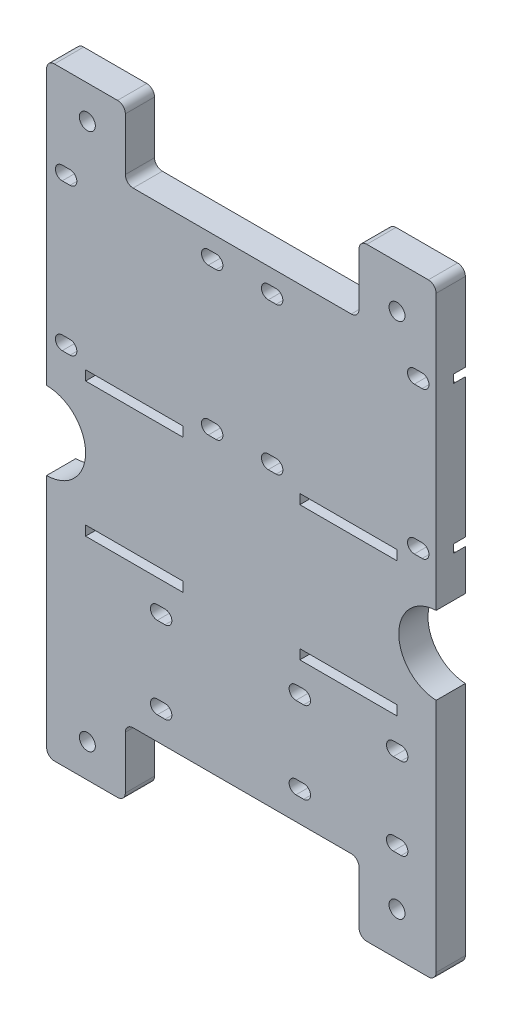
SolidWorks part; units mm, degrees
material "ABS"
ref_plane "Front Plane" through (0, 0, 0) normal (0, 0, 1) x (1, 0, 0)
ref_plane "Top Plane" through (0, 0, 0) normal (0, 1, 0) x (1, 0, 0)
ref_plane "Right Plane" through (0, 0, 0) normal (1, 0, 0) x (0, 0, -1)
sketch "Sketch1" plane through (0, 0, 0) normal (0, 0, 1) x (1, 0, 0)
  line L1 (0, 0) -> (100, 0)
  line L2 (0, 0) -> (0, 155)
  line L3 (0, 155) -> (100, 155)
  line L4 (100, 0) -> (100, 155)
  dimension "D1" = 100
  dimension "D2" = 155
extrude "Boss-Extrude1" add sketch "Sketch1" along normal blind 7.5
sketch "Sketch2" plane through (0, 0, 7.5) normal (0, 0, 1) x (1, 0, 0)
  line L0 (0, 77.5) -> (100, 77.5) construction
  line L1 (0, 155) -> (0, 0) construction
  line L2 (100, 0) -> (100, 155) construction
  line L3 (100, 155) -> (0, 155) construction
  line L4 (10.45, 146.45) -> (20.2, 146.45) construction
  line L5 (20.2, 137.5) -> (80.2, 137.5)
  line L6 (20.2, 137.5) -> (20.2, 155)
  line L7 (20.2, 155) -> (80.2, 155)
  line L8 (80.2, 137.5) -> (80.2, 155)
  line L9 (89.95, 143.95) -> (80.2, 143.95) construction
  line L10 (20.2, 0) -> (80.2, 0)
  line L11 (80.2, 17.5) -> (80.2, 0)
  line L12 (20.2, 17.5) -> (80.2, 17.5)
  line L13 (20.2, 17.5) -> (20.2, 0)
  circle A0 centre (10.45, 146.45) radius 2.05
  circle A1 centre (89.95, 143.95) radius 2.05
  circle A2 centre (89.95, 11.05) radius 2.05
  circle A3 centre (10.45, 8.55) radius 2.05
  dimension "D5" = 4.1
  dimension "D1" = 8.55
  dimension "D2" = 89.55
  dimension "D3" = 10.05
  dimension "D4" = 11.05
  dimension "D6" = 17.5
  dimension "D7" = 60
extrude "Hole cutouts" cut sketch "Sketch2" against normal through all
sketch "Sketch3" plane through (0, 0, 7.5) normal (0, 0, 1) x (1, 0, 0)
  line L0 (0, 72.5) -> (100, 72.5) construction
  line L1 (0, 155) -> (0, 0) construction
  line L2 (100, 0) -> (100, 155) construction
  line L3 (90, 56.5) -> (90, 54)
  line L4 (0, 56.5) -> (100, 56.5)
  line L5 (0, 56.5) -> (0, 88.5)
  line L6 (0, 88.5) -> (100, 88.5)
  line L7 (100, 56.5) -> (100, 88.5)
  line L8 (0, 56.5) -> (100, 88.5) construction
  line L9 (0, 88.5) -> (100, 56.5) construction
  line L10 (10, 88.5) -> (35, 88.5)
  line L11 (10, 88.5) -> (10, 91)
  line L12 (10, 91) -> (35, 91)
  line L13 (35, 88.5) -> (35, 91)
  line L14 (65, 88.5) -> (90, 88.5)
  line L15 (65, 88.5) -> (65, 91)
  line L16 (65, 91) -> (90, 91)
  line L17 (90, 88.5) -> (90, 91)
  line L18 (65, 54) -> (90, 54)
  line L19 (65, 56.5) -> (65, 54)
  line L20 (35, 56.5) -> (35, 54)
  line L21 (10, 56.5) -> (10, 54)
  line L22 (10, 54) -> (35, 54)
  line L23 (10, 56.5) -> (35, 56.5)
  line L24 (65, 56.5) -> (90, 56.5)
  point P6 (50, 72.5)
  point P27 (0, 77.5)
  dimension "D1" = 32
  dimension "D2" = 25
  dimension "D3" = 2.5
  dimension "D4" = 10
  dimension "D5" = 10
  dimension "D6" = 5
extrude "Battery strap holes" cut sketch "Sketch3" against normal through all contours L6 L13 L12 L11 | L6 L17 L16 L15 | L21 L22 L20 L4 | L4 L19 L18 L3 region at (77.5, 55.25, 7.5) region at (22.5, 55.25, 7.5) region at (77.5, 89.75, 7.5) region at (22.5, 89.75, 7.5)
sketch "Sketch4" plane through (0, 0, 7.5) normal (0, 0, 1) x (1, 0, 0)
  line L0 (0, 112.88) -> (100, 112.88) construction
  line L1 (0, 155) -> (0, 0) construction
  line L2 (100, 0) -> (100, 155) construction
  line L5 (4, 131.76) -> (6, 131.76) construction
  line L7 (4, 133.51) -> (6, 133.51)
  line L8 (5, 94) -> (42.5, 94)
  line L9 (5, 94) -> (5, 131.76)
  line L10 (5, 131.76) -> (42.5, 131.76)
  line L11 (42.5, 94) -> (42.5, 131.76)
  line L12 (5, 94) -> (42.5, 131.76) construction
  line L13 (5, 131.76) -> (42.5, 94) construction
  line L14 (4, 130.01) -> (6, 130.01)
  line L15 (10, 91) -> (35, 91) construction
  line L16 (41.5, 131.76) -> (43.5, 131.76) construction
  line L17 (41.5, 133.51) -> (43.5, 133.51)
  line L18 (41.5, 130.01) -> (43.5, 130.01)
  line L19 (41.5, 94) -> (43.5, 94) construction
  line L20 (41.5, 92.25) -> (43.5, 92.25)
  line L21 (41.5, 95.75) -> (43.5, 95.75)
  line L22 (4, 94) -> (6, 94) construction
  line L23 (4, 92.25) -> (6, 92.25)
  line L24 (4, 95.75) -> (6, 95.75)
  arc A0 (4, 133.51) -> (4, 130.01) centre (4, 131.76) ccw
  arc A1 (6, 130.01) -> (6, 133.51) centre (6, 131.76) ccw
  arc A2 (41.5, 133.51) -> (41.5, 130.01) centre (41.5, 131.76) ccw
  arc A3 (43.5, 130.01) -> (43.5, 133.51) centre (43.5, 131.76) ccw
  arc A4 (41.5, 92.25) -> (41.5, 95.75) centre (41.5, 94) cw
  arc A5 (43.5, 95.75) -> (43.5, 92.25) centre (43.5, 94) cw
  arc A6 (4, 92.25) -> (4, 95.75) centre (4, 94) cw
  arc A7 (6, 95.75) -> (6, 92.25) centre (6, 94) cw
  point P8 (5, 131.76)
  point P10 (23.75, 112.88)
  point P18 (42.5, 131.76)
  point P30 (42.5, 94)
  point P37 (5, 94)
  dimension "D4" = 1.75
  dimension "D7" = 1.75
  dimension "D1" = 5
  dimension "D2" = 37.5
  dimension "D3" = 37.76
  dimension "D5" = 2
  dimension "D6" = 3
  dimension "D8" = 2
extrude "H-Bridge Holes" cut sketch "Sketch4" against normal blind 7.5 contours L10 A1 L7 A0 L14 L9 | L14 A1 L10 L9 | L10 A2 L18 L11 | L18 A3 L17 A2 L10 L11 | A7 L8 L9 L24 A6 L23 | A7 L24 L9 L8 | A5 L21 L11 L8 A4 L20 | A4 L8 L11 L21 region at (4.5936, 132.0261, 7.5) region at (6.2193, 130.9616, 7.5) region at (42.9064, 132.0261, 7.5) region at (41.2807, 130.9616, 7.5) region at (6.2193, 94.7984, 7.5) region at (4.5936, 93.7339, 7.5) region at (42.9064, 93.7339, 7.5) region at (41.2807, 94.7984, 7.5)
sketch "Sketch6" plane through (0, 0, 7.5) normal (0, 0, 1) x (1, 0, 0)
  line L0 (0, 35.75) -> (100, 35.75) construction
  line L1 (0, 155) -> (0, 0) construction
  line L2 (100, 0) -> (100, 155) construction
  line L3 (26, 54) -> (26, 17.5) construction
  line L4 (10, 54) -> (35, 54) construction
  line L5 (80.2, 17.5) -> (20.2, 17.5) construction
  line L6 (66, 46.25) -> (64, 46.25) construction
  line L7 (65, 25.25) -> (90, 25.25)
  line L8 (65, 25.25) -> (65, 46.25)
  line L9 (65, 46.25) -> (90, 46.25)
  line L10 (90, 25.25) -> (90, 46.25)
  line L11 (65, 25.25) -> (90, 46.25) construction
  line L12 (65, 46.25) -> (90, 25.25) construction
  line L13 (66, 44.5) -> (64, 44.5)
  line L14 (66, 48) -> (64, 48)
  line L15 (89, 46.25) -> (91, 46.25) construction
  line L16 (89, 48) -> (91, 48)
  line L17 (89, 44.5) -> (91, 44.5)
  line L18 (89, 25.25) -> (91, 25.25) construction
  line L19 (89, 23.5) -> (91, 23.5)
  line L20 (89, 27) -> (91, 27)
  line L21 (66, 25.25) -> (64, 25.25) construction
  line L22 (66, 27) -> (64, 27)
  line L23 (66, 23.5) -> (64, 23.5)
  arc A0 (66, 44.5) -> (66, 48) centre (66, 46.25) ccw
  arc A1 (64, 48) -> (64, 44.5) centre (64, 46.25) ccw
  arc A2 (89, 48) -> (89, 44.5) centre (89, 46.25) ccw
  arc A3 (91, 44.5) -> (91, 48) centre (91, 46.25) ccw
  arc A4 (89, 23.5) -> (89, 27) centre (89, 25.25) cw
  arc A5 (91, 27) -> (91, 23.5) centre (91, 25.25) cw
  arc A6 (66, 27) -> (66, 23.5) centre (66, 25.25) cw
  arc A7 (64, 23.5) -> (64, 27) centre (64, 25.25) cw
  point P12 (26, 35.75)
  point P13 (77.5, 35.75)
  point P20 (65, 46.25)
  point P25 (90, 46.25)
  point P36 (90, 25.25)
  point P43 (65, 25.25)
  dimension "D4" = 1.75
  dimension "D1" = 21
  dimension "D2" = 25
  dimension "D3" = 10
  dimension "D5" = 2
  dimension "D6" = 26
extrude "Battery Protection Board Holes" cut sketch "Sketch6" against normal through all contours L14 A1 L13 L8 L9 A0 | L13 A0 L9 L8 | L9 A2 L17 L10 | L17 A3 L16 A2 L9 L10 | A5 L20 L10 L7 A4 L19 | A4 L7 L10 L20 | A7 L23 A6 L7 L8 L22 | A6 L22 L8 L7 region at (66.2193, 26.0484, 7.5) region at (64.5936, 24.9839, 7.5) region at (88.7807, 26.0484, 7.5) region at (90.4064, 24.9839, 7.5) region at (64.5936, 46.5161, 7.5) region at (66.2193, 45.4516, 7.5) region at (88.7807, 45.4516, 7.5) region at (90.4064, 46.5161, 7.5)
sketch "Sketch7" plane through (0, 0, 7.5) normal (0, 0, 1) x (1, 0, 0)
  line L0 (0, 35.75) -> (100, 35.75) construction
  line L1 (0, 155) -> (0, 0) construction
  line L2 (100, 0) -> (100, 155) construction
  line L3 (29.4, 54) -> (29.4, 17.5) construction
  line L4 (10, 54) -> (35, 54) construction
  line L5 (80.2, 17.5) -> (20.2, 17.5) construction
  line L6 (28.4, 46.25) -> (30.4, 46.25) construction
  line L7 (10, 27.25) -> (32.4, 27.25)
  line L8 (10, 27.25) -> (10, 44.25)
  line L9 (10, 44.25) -> (32.4, 44.25)
  line L10 (32.4, 27.25) -> (32.4, 44.25)
  line L11 (10, 27.25) -> (32.4, 44.25) construction
  line L12 (10, 44.25) -> (32.4, 27.25) construction
  line L13 (28.4, 48) -> (30.4, 48)
  line L14 (28.4, 44.5) -> (30.4, 44.5)
  line L15 (28.4, 25.25) -> (30.4, 25.25) construction
  line L16 (28.4, 23.5) -> (30.4, 23.5)
  line L17 (28.4, 27) -> (30.4, 27)
  arc A0 (28.4, 48) -> (28.4, 44.5) centre (28.4, 46.25) ccw
  arc A1 (30.4, 44.5) -> (30.4, 48) centre (30.4, 46.25) ccw
  arc A2 (28.4, 23.5) -> (28.4, 27) centre (28.4, 25.25) cw
  arc A3 (30.4, 27) -> (30.4, 23.5) centre (30.4, 25.25) cw
  point P12 (29.4, 35.75)
  point P13 (21.2, 35.75)
  point P20 (29.4, 46.25)
  point P28 (29.4, 25.25)
  dimension "D6" = 1.75
  dimension "D1" = 3
  dimension "D2" = 17
  dimension "D3" = 22.4
  dimension "D4" = 10
  dimension "D5" = 10.5
  dimension "D7" = 2
extrude "Voltage Step Down Board" cut sketch "Sketch7" against normal through all contours L14 A1 L13 A0 | L16 A3 L17 A2
fillet "Fillet1" radius 2 12 edges at (0, 0, 3.75) (20.2, 0, 3.75) (20.2, 17.5, 3.75) (80.2, 17.5, 3.75) (80.2, 0, 3.75) (100, 0, 3.75) (100, 155, 3.75) (80.2, 155, 3.75) (80.2, 137.5, 3.75) (20.2, 137.5, 3.75) (20.2, 155, 3.75) (0, 155, 3.75)
ref_plane "Plane1" through (50.2, 0, 0) normal (1, 0, 0) x (0, 0, -1)
sketch "Sketch9" plane through (0, 0, 7.5) normal (0, 0, 1) x (1, 0, 0)
  line L0 (0, 72.5) -> (100, 72.5) construction
  line L1 (0, 153) -> (0, 2) construction
  line L2 (100, 2) -> (100, 153) construction
  line L3 (22.5, 88.5) -> (22.5, 56.5) construction
  line L4 (10, 88.5) -> (35, 88.5) construction
  line L5 (10, 56.5) -> (35, 56.5) construction
  line L6 (0, 82.5) -> (0, 62.5)
  arc A0 (0, 82.5) -> (0, 62.5) centre (0, 72.5) cw
  point P12 (22.5, 72.5)
  dimension "D1" = 10
extrude "Camera Wire Hole" cut sketch "Sketch9" against normal through all
mirror "Mirror1" about plane through (50.2, 0, 0) normal (1, 0, 0) of "H-Bridge Holes", "Camera Wire Hole"
sketch "Sketch10" plane through (0, 0, 0) normal (0, 0, -1) x (-1, 0, 0)
  line L0 (-96.4, 95.75) -> (-94.4, 95.75) construction
  line L1 (-96.4, 92.25) -> (-94.4, 92.25) construction
  line L2 (-58.9, 92.25) -> (-56.9, 92.25) construction
  line L3 (-58.9, 95.75) -> (-56.9, 95.75) construction
  line L4 (-58.9, 133.51) -> (-56.9, 133.51) construction
  line L5 (-58.9, 130.01) -> (-56.9, 130.01) construction
  line L6 (-96.4, 133.51) -> (-94.4, 133.51) construction
  line L7 (-96.4, 130.01) -> (-94.4, 130.01) construction
  line L8 (-96.4, 95.75) -> (-94.4, 95.75)
  line L9 (-96.4, 92.25) -> (-94.4, 92.25)
  line L10 (-58.9, 92.25) -> (-56.9, 92.25)
  line L11 (-58.9, 95.75) -> (-56.9, 95.75)
  line L12 (-58.9, 133.51) -> (-56.9, 133.51)
  line L13 (-58.9, 130.01) -> (-56.9, 130.01)
  line L14 (-96.4, 133.51) -> (-94.4, 133.51)
  line L15 (-96.4, 130.01) -> (-94.4, 130.01)
  line L16 (-96.4, 131.76) -> (-94.4, 131.76) construction
  line L17 (-96.4, 135.51) -> (-94.4, 135.51)
  line L18 (-96.4, 128.01) -> (-94.4, 128.01)
  line L19 (-58.9, 131.76) -> (-56.9, 131.76) construction
  line L20 (-58.9, 135.51) -> (-56.9, 135.51)
  line L21 (-58.9, 128.01) -> (-56.9, 128.01)
  line L22 (-96.4, 94) -> (-94.4, 94) construction
  line L23 (-96.4, 97.75) -> (-94.4, 97.75)
  line L24 (-96.4, 90.25) -> (-94.4, 90.25)
  line L25 (-58.9, 94) -> (-56.9, 94) construction
  line L26 (-58.9, 97.75) -> (-56.9, 97.75)
  line L27 (-58.9, 90.25) -> (-56.9, 90.25)
  arc A0 (-94.4, 92.25) -> (-94.4, 95.75) centre (-94.4, 94) ccw construction
  arc A1 (-96.4, 95.75) -> (-96.4, 92.25) centre (-96.4, 94) ccw construction
  arc A2 (-56.9, 92.25) -> (-56.9, 95.75) centre (-56.9, 94) ccw construction
  arc A3 (-58.9, 95.75) -> (-58.9, 92.25) centre (-58.9, 94) ccw construction
  arc A4 (-56.9, 130.01) -> (-56.9, 133.51) centre (-56.9, 131.76) ccw construction
  arc A5 (-58.9, 133.51) -> (-58.9, 130.01) centre (-58.9, 131.76) ccw construction
  arc A6 (-96.4, 133.51) -> (-96.4, 130.01) centre (-96.4, 131.76) ccw construction
  arc A7 (-94.4, 130.01) -> (-94.4, 133.51) centre (-94.4, 131.76) ccw construction
  arc A8 (-94.4, 92.25) -> (-94.4, 95.75) centre (-94.4, 94) ccw
  arc A9 (-96.4, 95.75) -> (-96.4, 92.25) centre (-96.4, 94) ccw
  arc A10 (-56.9, 92.25) -> (-56.9, 95.75) centre (-56.9, 94) ccw
  arc A11 (-58.9, 95.75) -> (-58.9, 92.25) centre (-58.9, 94) ccw
  arc A12 (-56.9, 130.01) -> (-56.9, 133.51) centre (-56.9, 131.76) ccw
  arc A13 (-58.9, 133.51) -> (-58.9, 130.01) centre (-58.9, 131.76) ccw
  arc A14 (-96.4, 133.51) -> (-96.4, 130.01) centre (-96.4, 131.76) ccw
  arc A15 (-94.4, 130.01) -> (-94.4, 133.51) centre (-94.4, 131.76) ccw
  arc A16 (-96.4, 135.51) -> (-96.4, 128.01) centre (-96.4, 131.76) ccw
  arc A17 (-94.4, 128.01) -> (-94.4, 135.51) centre (-94.4, 131.76) ccw
  arc A18 (-58.9, 135.51) -> (-58.9, 128.01) centre (-58.9, 131.76) ccw
  arc A19 (-56.9, 128.01) -> (-56.9, 135.51) centre (-56.9, 131.76) ccw
  arc A20 (-96.4, 97.75) -> (-96.4, 90.25) centre (-96.4, 94) ccw
  arc A21 (-94.4, 90.25) -> (-94.4, 97.75) centre (-94.4, 94) ccw
  arc A22 (-58.9, 97.75) -> (-58.9, 90.25) centre (-58.9, 94) ccw
  arc A23 (-56.9, 90.25) -> (-56.9, 97.75) centre (-56.9, 94) ccw
  point P4 (-95.4, 131.76)
  point P17 (-57.9, 131.76)
  point P28 (-95.4, 94)
  point P39 (-57.9, 94)
  dimension "D1" = 3.75
extrude "Bore Holes" cut sketch "Sketch10" against normal blind 3
